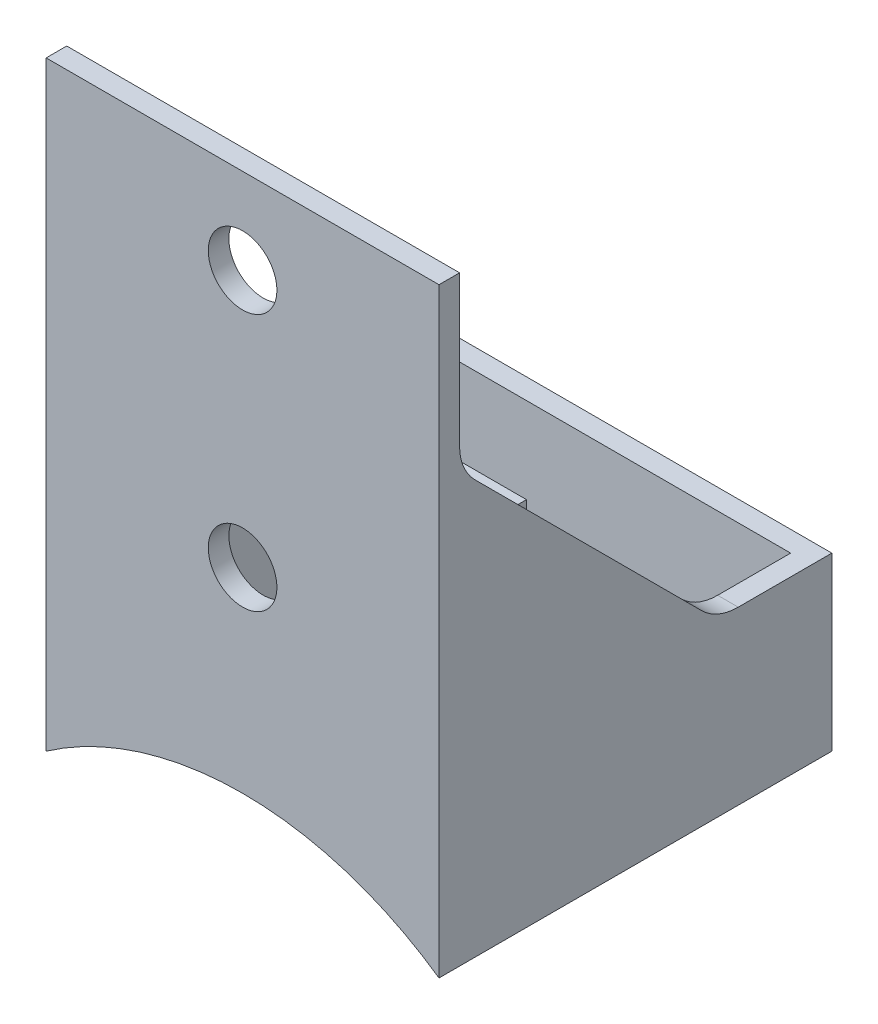
SolidWorks part; units mm, degrees
ref_plane "前视基准面" through (0, 0, 0) normal (0, 0, 1) x (1, 0, 0)
ref_plane "上视基准面" through (0, 0, 0) normal (0, 1, 0) x (1, 0, 0)
ref_plane "右视基准面" through (0, 0, 0) normal (1, 0, 0) x (0, 0, -1)
sketch "草图1" plane through (0, 0, 0) normal (0, 1, 0) x (1, 0, 0)
  line L0 (0, -1000) -> (0, 49000) construction
  line L1 (-10.25, 10.25) -> (10.25, 10.25)
  line L2 (-10.25, 10.25) -> (-10.25, -10.25)
  line L3 (-10.25, -10.25) -> (10.25, -10.25)
  line L4 (10.25, 10.25) -> (10.25, -10.25)
  line L5 (-10.25, 10.25) -> (10.25, -10.25) construction
  line L6 (-10.25, -10.25) -> (10.25, 10.25) construction
  line L7 (-5.15, 7.65) -> (-5.15, 10.25)
  line L8 (-11.45, 11.45) -> (11.45, 11.45)
  line L9 (-11.45, 11.45) -> (-11.45, -11.45)
  line L10 (-11.45, -11.45) -> (11.45, -11.45)
  line L11 (11.45, 11.45) -> (11.45, -11.45)
  line L12 (-11.45, 11.45) -> (11.45, -11.45) construction
  line L13 (-11.45, -11.45) -> (11.45, 11.45) construction
  line L14 (-7.62, 5.18) -> (-10.25, 5.18)
  line L15 (5.15, 7.65) -> (5.15, 10.25)
  line L16 (-10.25, 10.25) -> (-10.25, -10.25)
  line L17 (10.25, 10.25) -> (10.25, -10.25)
  line L18 (7.62, 5.18) -> (10.25, 5.18)
  line L19 (-10.25, -10.25) -> (-11.45, -10.25)
  line L20 (10.25, -10.25) -> (11.45, -10.25)
  circle A1 centre (-7.62, 7.65) radius 1.27
  arc A3 (-7.62, 5.18) -> (-5.15, 7.65) centre (-7.62, 7.65) ccw
  arc A4 (-5.15, 7.65) -> (-9.3815, 9.3815) centre (-7.62, 7.65) ccw construction
  arc A5 (-9.3815, 9.3815) -> (-7.62, 5.18) centre (-7.62, 7.65) ccw construction
  arc A6 (7.62, 5.18) -> (5.15, 7.65) centre (7.62, 7.65) cw
  circle A7 centre (7.62, 7.65) radius 1.27
  arc A8 (9.3815, 9.3815) -> (7.62, 5.18) centre (7.62, 7.65) cw construction
  arc A9 (5.15, 7.65) -> (9.3815, 9.3815) centre (7.62, 7.65) cw construction
  point P0 (0, 0)
  point P12 (0, 0)
  dimension "D3" = 2.54
  dimension "D4" = 15.24
  dimension "D5" = 2.6
  dimension "D8" = 1.2
  dimension "D1" = 20.5
  dimension "D2" = 20.5
  dimension "D6" = 1.2
  dimension "D7" = 1.2
extrude "凸台-拉伸1" add sketch "草图1" along normal blind 10 contours L11 L8 L9 L10 L1 L4 L17 L3 L2 | L20 L3 L19 L9 L10 L11 region at (-10.5655, 0, -7.715) region at (0, 0, 10.85)
extrude "凸台-拉伸2" add sketch "草图1<4>" along normal blind 5 contours L14 A3 L7 L1 L2 A1 | A6 L18 L4 L1 L15 A7 region at (-7.7, 0, -10.1781) region at (7.7, 0, -10.1781)
sketch "草图1<4>" plane through (0, 0, 0) normal (0, 1, 0) x (1, 0, 0) same geometry as "草图1"
extrude "凸台-拉伸3" add sketch "草图1<5>" along normal blind 10 contours L20 L3 L19 L9 L10 L11 region at (0, 0, 10.85)
sketch "草图1<5>" plane through (0, 0, 0) normal (0, 1, 0) x (1, 0, 0) same geometry as "草图1"
sketch "草图3" plane through (0, 10, 0) normal (0, 1, 0) x (1, 0, 0)
  line L0 (-11.45, 11.45) -> (-11.45, -11.45) construction
  line L1 (-11.45, -10.25) -> (11.45, -10.25)
  line L2 (-11.45, -10.25) -> (-11.45, -11.45)
  line L3 (-11.45, -11.45) -> (11.45, -11.45)
  line L4 (11.45, -10.25) -> (11.45, -11.45)
extrude "凸台-拉伸4" add sketch "草图3" along normal blind 25
sketch "草图4" plane through (0, 0, -11.45) normal (0, 0, -1) x (-1, 0, 0)
  circle A0 centre (0, -16.3981) radius 20
  dimension "D1" = 40
extrude "切除-拉伸1" cut sketch "草图4" against normal up to next
sketch "草图5" plane through (0, 0, 10.25) normal (0, 0, -1) x (-1, 0, 0)
  line L1 (-11.45, 35) -> (11.45, 35) construction
  circle A0 centre (0, 15) radius 2
  circle A1 centre (0, 30) radius 2
  point P9 (0, 35)
  dimension "D1" = 4
  dimension "D2" = 4
  dimension "D4" = 15
  dimension "D3" = 5
extrude "切除-拉伸2" cut sketch "草图5" against normal through all
chamfer "倒角1" distance 15 angle 45 2 edges at (10.85, 10, 10.25) (-10.85, 10, 10.25)
fillet "圆角1" radius 3 4 edges at (10.85, 10, -4.75) (10.85, 25, 10.25) (-10.85, 25, 10.25) (-10.85, 10, -4.75)
